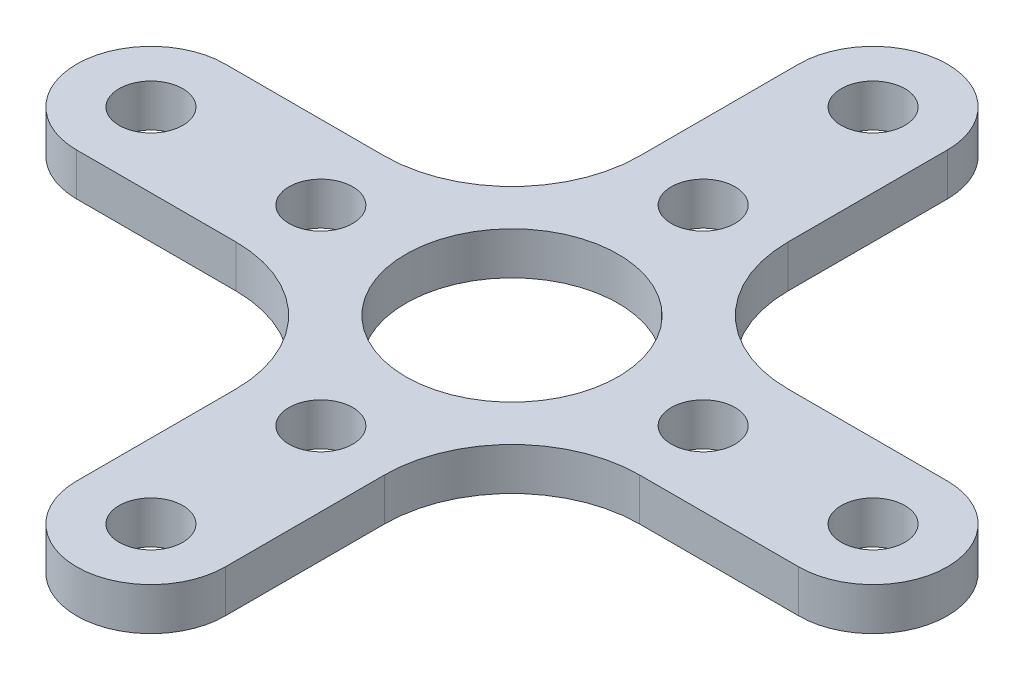
SolidWorks part; units mm, degrees
ref_plane "Front Plane" through (0, 0, 0) normal (0, 0, 1) x (1, 0, 0)
ref_plane "Top Plane" through (0, 0, 0) normal (0, 1, 0) x (1, 0, 0)
ref_plane "Right Plane" through (0, 0, 0) normal (1, 0, 0) x (0, 0, -1)
sketch "Sketch1" plane through (0, 0, 0) normal (0, 1, 0) x (1, 0, 0)
  line L0 (0, -20.5) -> (0, 20.5) construction
  line L1 (-20.5, 0) -> (20.5, 0) construction
  line L2 (-17, 3.5) -> (-3.5, 3.5) construction
  line L3 (-3.5, 3.5) -> (-3.5, 17) construction
  line L4 (3.5, 17) -> (3.5, 3.5) construction
  line L5 (3.5, 3.5) -> (17, 3.5) construction
  line L6 (3.5, -3.5) -> (17, -3.5) construction
  line L7 (3.5, -17) -> (3.5, -3.5) construction
  line L8 (-3.5, -3.5) -> (-3.5, -17) construction
  line L9 (-17, -3.5) -> (-3.5, -3.5) construction
  line L10 (-3.5, 17) -> (-3.5, 9.5)
  line L11 (3.5, 17) -> (3.5, 9.5)
  line L12 (9.5, 3.5) -> (17, 3.5)
  line L13 (17, -3.5) -> (9.5, -3.5)
  line L14 (3.5, -9.5) -> (3.5, -17)
  line L15 (-3.5, -17) -> (-3.5, -9.5)
  line L16 (-9.5, -3.5) -> (-17, -3.5)
  line L17 (-17, 3.5) -> (-9.5, 3.5)
  arc A1 (-3.5, 17) -> (3.5, 17) centre (0, 17) cw
  arc A2 (-3.5, -17) -> (3.5, -17) centre (0, -17) ccw
  arc A3 (-17, 3.5) -> (-17, -3.5) centre (-17, 0) ccw
  arc A4 (17, 3.5) -> (17, -3.5) centre (17, 0) cw
  arc A5 (-9.5, 3.5) -> (-3.5, 9.5) centre (-9.5, 9.5) ccw
  arc A6 (3.5, 9.5) -> (9.5, 3.5) centre (9.5, 9.5) ccw
  arc A7 (9.5, -3.5) -> (3.5, -9.5) centre (9.5, -9.5) ccw
  arc A8 (-3.5, -9.5) -> (-9.5, -3.5) centre (-9.5, -9.5) ccw
  point P4 (-9.5, 3.5)
  point P11 (-3.5, 9.5)
  point P38 (0, 0)
  dimension "D1" = 41
  dimension "D2" = 41
  dimension "D3" = 3.5
  dimension "D4" = 3.5
  dimension "D5" = 11
  dimension "D6" = 11
  dimension "D7" = 4
extrude "Boss-Extrude1" add sketch "Sketch1" along normal blind 2
sketch "Sketch2" plane through (0, 2, 0) normal (0, 1, 0) x (1, 0, 0)
  circle A0 centre (0, 17) radius 1.5
  circle A1 centre (0, 9) radius 1.5
  circle A2 centre (0, 0) radius 5
  circle A3 centre (17, 0) radius 1.5
  circle A4 centre (9, 0) radius 1.5
  circle A5 centre (0, -17) radius 1.5
  circle A6 centre (0, -9) radius 1.5
  circle A7 centre (-17, 0) radius 1.5
  circle A8 centre (-9, 0) radius 1.5
  point P7 (8.3886, -2.5627)
  point P8 (0.2397, 0)
  point P9 (0, 0)
  point P22 (0, 0)
  dimension "D1" = 3
  dimension "D2" = 3
  dimension "D3" = 10
  dimension "D4" = 9
  dimension "D5" = 17
  dimension "D6" = 4
extrude "Cut-Extrude1" cut sketch "Sketch2" against normal blind 2
